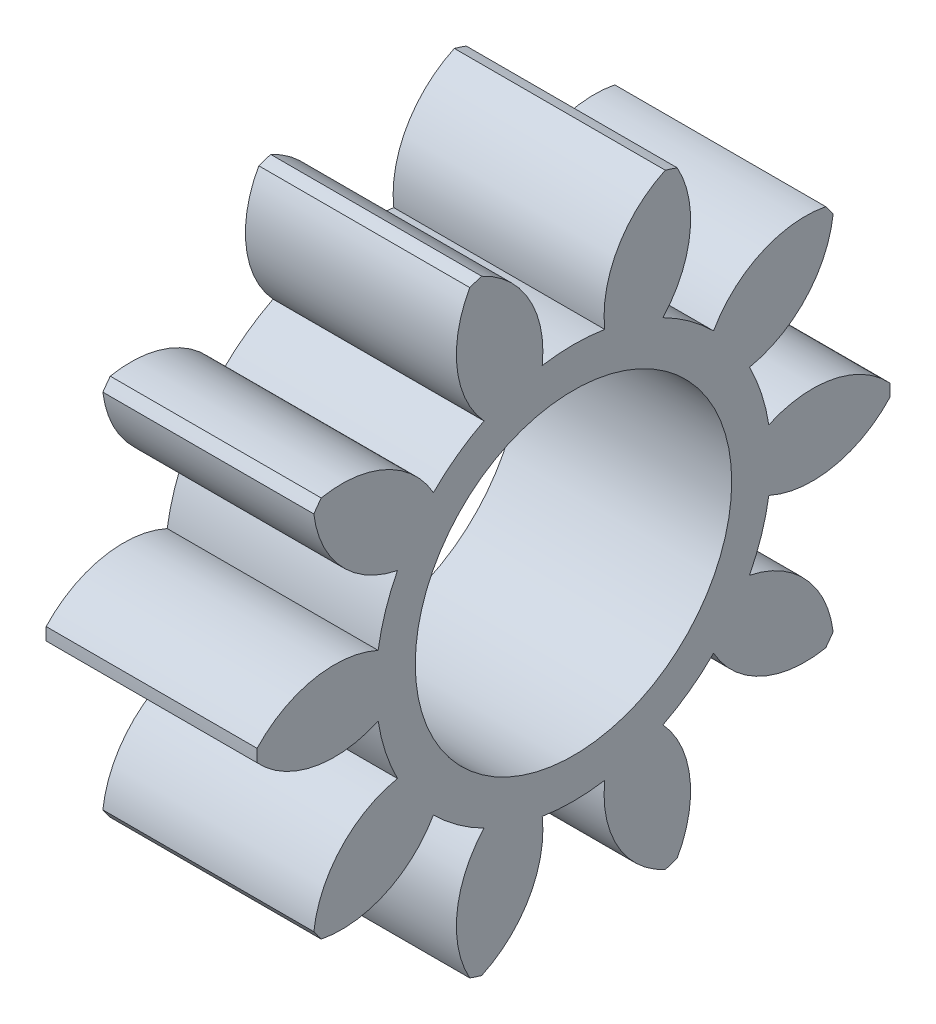
SolidWorks part; units mm, degrees
ref_plane "Plane1" through (0, 0, 0) normal (0, 0, 1) x (1, 0, 0)
ref_plane "Plane2" through (0, 0, 0) normal (0, 1, 0) x (1, 0, 0)
ref_plane "Plane3" through (0, 0, 0) normal (1, 0, 0) x (0, 0, -1)
other "Configuration Table"
sketch "HoldingSke" plane through (0, 0, 0) normal (0, 1, 0) x (1, 0, 0)
  line L0 (0, 0) -> (0.9848, -0.1736)
  line L1 (-15, 0) -> (100, 0) construction
  line L2 (0, 0) -> (-2.1039, 2.3779)
  line L3 (0, 0) -> (-11.863, 4.5341)
  line L4 (0, 0) -> (8.5048, 1.4996)
  line L5 (0, 0) -> (-46.8476, -17.4728)
  line L6 (0, 0) -> (-3.3159, -2.2372)
  line L7 (-2.1039, 2.3779) -> (8.6586, 51.2059)
  line L8 (-76.2, 54.61) -> (-75.2, 54.61)
  line L9 (-71.009, 38.7566) -> (-53.1078, 45.2721)
  line L10 (-76.2, 71.12) -> (104.1128, 71.12)
  line L11 (0, 0) -> (-4, 0)
  line L12 (-76.2, 101.6) -> (-76.162, 101.6)
  line L13 (24.9733, 27.94) -> (52.9518, 28.4284)
  line L14 (24.9733, 27.94) -> (24.9743, 27.94)
  line L15 (24.9733, 27.94) -> (100.4006, 29.5858)
  line L16 (-63.627, -1) -> (-12.827, -1)
  circle A0 centre (0, 0) radius 3
  circle A1 centre (0, 0) radius 3.749
  circle A2 centre (0, 0) radius 37.5
  circle A3 centre (0, 0) radius 3
  dimension "Num_teeth" = 10
  dimension "Pitch_radius" = 180.3128
  dimension "Width" = 4
  dimension "Thickness" = 4
sketch "BasProSke" plane through (0, 0, 0) normal (0, 1, 0) x (1, 0, 0)
  line L0 (-10, 0) -> (60, 0) construction
  line L1 (0, 0) -> (0, 6)
  line L2 (0, 0) -> (4, 0)
  line L3 (4, 0) -> (4, 6)
  line L4 (4, 6) -> (0, 6)
  dimension "Thickness" = 4
  dimension "Diameter" = 12
revolve "Base-Revolve" add sketch "BasProSke" angle 360 about L0
sketch "TooCutSke" plane through (0, 0, 0) normal (1, 0, 0) x (0, 0, -1)
  line L1 (0, 0) -> (0, 107) construction
  line L2 (0, 0) -> (-0.8485, 4.9275) construction
  line L3 (0, 0) -> (-3.0584, 9.4126) construction
  line L4 (-0.8485, 4.9275) -> (-1.5292, 4.7063) construction
  arc A0 (0.5928, 3.7018) -> (-0.5928, 3.7018) centre (0, 0) ccw
  arc A1 (1.7758, 5.7578) -> (-1.7758, 5.7578) centre (0, 0) ccw
  circle A2 centre (0, 0) radius 5 construction
  circle A3 centre (0, 0) radius 4.6985 construction
  arc A4 (-0.5928, 3.7018) -> (-1.7758, 5.7578) centre (-2.5801, 3.9267) ccw
  arc A5 (1.7758, 5.7578) -> (0.5928, 3.7018) centre (2.5801, 3.9267) ccw
extrude "ToothCut" cut sketch "TooCutSke" along normal through all
fillet "Breaks" [suppressed] radius 0.02 tangent propagation no
fillet "RootFillets" [suppressed] radius 0.251
pattern_circular "TeethCuts" count 10 every 36 about axis through (-10, 0, 0) along (1, 0, 0) of "ToothCut", "RootFillets", "Breaks"
sketch "HubNeaOneSke" plane through (0, 0, 0) normal (-1, 0, 0) x (0, 0, 1)
  circle A0 centre (0, 0) radius 3.749
  dimension "Diameter" = 7.498
extrude "HubNearOne" [suppressed] add sketch "HubNeaOneSke" along normal blind 46.0001
sketch "HubNeaBotSke" plane through (0, 0, 0) normal (-1, 0, 0) x (0, 0, 1)
  circle A0 centre (0, 0) radius 3.749
  dimension "Diameter" = 7.498
extrude "HubNearBoth" [suppressed] add sketch "HubNeaBotSke" along normal blind 23
ref_plane "FarPln" through (4, 0, 0) normal (1, 0, 0) x (0, 0, -1)
sketch "HubFarSke" plane through (4, 0, 0) normal (1, 0, 0) x (0, 0, -1)
  circle A0 centre (0, 0) radius 3.749
  dimension "Diameter" = 7.498
extrude "HubFar" [suppressed] add sketch "HubFarSke" along normal blind 23
sketch "BorSke" plane through (0, 0, 0) normal (1, 0, 0) x (0, 0, -1)
  circle A0 centre (0, 0) radius 3
  dimension "Diameter" = 6
extrude "Bore" cut sketch "BorSke" along normal mid plane 100.0001
sketch "KeySke" plane through (0, 0, 0) normal (1, 0, 0) x (0, 0, -1)
  line L0 (-1, 0) -> (-1, 4)
  line L1 (-1, 4) -> (1, 4)
  line L2 (1, 4) -> (1, 0)
  line L3 (0, 0) -> (0, 34) construction
  line L4 (-1, 0) -> (1, 0)
  dimension "Width" = 2
extrude "Keyway" [suppressed] cut sketch "KeySke" along normal mid plane 100.0001
pattern_circular "Keyway2" [suppressed] count 2 every 90 about axis through (-10, 0, 0) along (1, 0, 0)
ref_axis "Axis1" through (4, 0, 0) along (-1, 0, 0)
sketch "Sketch1" plane through (0, 0, 0) normal (-1, 0, 0) x (0, 0, 1)
  line L0 (1, 2.8284) -> (1, -2.8284)
  line L1 (1, 0) -> (-3, 0) construction
  circle A0 centre (0, 0) radius 3 construction
  arc A1 (1, 2.8284) -> (1, -2.8284) centre (0, 0) cw
  dimension "D1" = 4
equation "' \"Module@HoldingSke\" = 6.35"
equation "' \"Num_teeth@HoldingSke\" = 12"
equation "' \"Ap@HoldingSke\" =  20"
equation "' \"Ap@HoldingSke\" = 20"
equation "' \"Width@HoldingSke\" = 0.5 * 25.4"
equation "' \"Hub_dia@HoldingSke\"= 1 * 25.4"
equation "' \"Hub_dia@HoldingSke\" = 1 * 25.4"
equation "' \"Overall_len@HoldingSke\" = 1.0 * 25.4"
equation "' \"Bore@HoldingSke\" = 0.75 * 25.4"
equation "' \"T_dim@HoldingSke\" = 0.1 * 25.4"
equation "' \"Width@KeySke\" = 0.25 * 25.4"
equation "' \"Show_teeth@HoldingSke\" = 13"
equation "' \"Backlash@HoldingSke\" = 0.009 * 25.4"
equation "' \"Addendum_fac@HoldingSke\" = 1.0"
equation "' \"Dedendum_fac@HoldingSke\" = 1.25"
equation "' \"Dedendum_add@HoldingSke\" = 0.00005 * 25.4"
equation "' \"Clearance_fac@HoldingSke\" = 0.25"
equation "\"Pitch@HoldingSke\" = 1 / \"Module@HoldingSke\""
equation "\"Overcut_dia@TooCutSke\" = (\"Num_teeth@HoldingSke\" + 2 * \"Addendum_fac@HoldingSke\") / \"Pitch@HoldingSke\" + 0.002 * 25.4"
equation "\"Pitch_dia@TooCutSke\" = \"Num_teeth@HoldingSke\" / \"Pitch@HoldingSke\""
equation "\"Base_dia@TooCutSke\" = \"Num_teeth@HoldingSke\" / \"Pitch@HoldingSke\" * cos((\"Ap@HoldingSke\"  * 3.14159265 / 180))"
equation "\"Root_dia@TooCutSke\" = (\"Num_teeth@HoldingSke\" + 2) / \"Pitch@HoldingSke\" - 2 * (\"Addendum_fac@HoldingSke\" + \"Dedendum_fac@HoldingSke\") / \"Pitch@HoldingSke\" - \"Dedendum_add@HoldingSke\" * 2"
equation "\"Half_ang@TooCutSke\" = 180 / \"Num_teeth@HoldingSke\""
equation "\"Half_CT@TooCutSke\" = \"Num_teeth@HoldingSke\" / \"Pitch@HoldingSke\" * sin((3.14159265 / 2 / \"Num_teeth@HoldingSke\")) / 2 - 7 * \"Backlash@HoldingSke\" / 4"
equation "\"Flank_rad@TooCutSke\" = \"Num_teeth@HoldingSke\" / \"Pitch@HoldingSke\" / 5"
equation "\"Radius@RootFillets\" = \"Clearance_fac@HoldingSke\" / \"Pitch@HoldingSke\" + \"Dedendum_add@HoldingSke\""
equation "\"Break_rad@Breaks\" = 0.02 / \"Pitch@HoldingSke\""
equation "\"Thickness@HoldingSke\" = \"Width@HoldingSke\""
equation "\"OAL@HoldingSke\" = \"Thickness@HoldingSke\""
equation "\"MHD@HoldingSke\" = (\"Num_teeth@HoldingSke\" + 2) / \"Pitch@HoldingSke\" - 2 * (\"Addendum_fac@HoldingSke\" + \"Dedendum_fac@HoldingSke\")  / \"Pitch@HoldingSke\" - \"Dedendum_add@HoldingSke\" * 2"
equation "\"MBD@HoldingSke\" = (\"Num_teeth@HoldingSke\" + 2) / \"Pitch@HoldingSke\" - 2 * (\"Addendum_fac@HoldingSke\" + \"Dedendum_fac@HoldingSke\")  / \"Pitch@HoldingSke\" - \"Dedendum_add@HoldingSke\" * 2 - 0.002 * 25.4"
equation "\"MHD@HoldingSke\" = ((sgn( \"MHD@HoldingSke\" - \"Hub_dia@HoldingSke\" )-1)*( \"MHD@HoldingSke\" - \"Hub_dia@HoldingSke\" ))/-2+ \"Hub_dia@HoldingSke\""
equation "\"MBD@HoldingSke\" = ((sgn( \"MBD@HoldingSke\" - \"Bore@HoldingSke\" )-1)*( \"MBD@HoldingSke\" - \"Bore@HoldingSke\" ))/-2+ \"Bore@HoldingSke\""
equation "\"OAL@HoldingSke\" = ((sgn( \"OAL@HoldingSke\" - \"Overall_len@HoldingSke\" )+1)*( \"OAL@HoldingSke\" - \"Overall_len@HoldingSke\" ))/2 + \"Overall_len@HoldingSke\" + 0.000002 * 25.4"
equation "\"Num_teeth@TeethCuts\" = int( \"Show_teeth@HoldingSke\" ) + 1"
equation "\"Num_teeth@TeethCuts\" = ((sgn( \"Num_teeth@TeethCuts\" - \"Num_teeth@HoldingSke\" )-1)*( \"Num_teeth@TeethCuts\" - \"Num_teeth@HoldingSke\" ))/-2+ \"Num_teeth@HoldingSke\""
equation "\"Num_teeth@TeethCuts\" = ((sgn( \"Num_teeth@TeethCuts\" - 2.0)+1)*( \"Num_teeth@TeethCuts\" - 2.0))/2 +2.0"
equation "\"Angle@TeethCuts\" = 360.0 / \"Num_teeth@HoldingSke\""
equation "\"Diameter@BasProSke\" = (\"Num_teeth@HoldingSke\" + 2 * \"Addendum_fac@HoldingSke\") / \"Pitch@HoldingSke\""
equation "\"Thickness@BasProSke\"  = \"Thickness@HoldingSke\""
equation "' \"Fillet_rad@BasProSke\" =  \"Thickness@HoldingSke\" * 0.05"
equation "' \"Fillet_rad@BasProSke\" = \"Thickness@HoldingSke\" * 0.05"
equation "\"MHD@HoldingSke\" = ((sgn( \"MHD@HoldingSke\" - \"Root_dia@TooCutSke\" )-1)*( \"MHD@HoldingSke\" - \"Root_dia@TooCutSke\" ))/-2+ \"Root_dia@TooCutSke\""
equation "\"Diameter@HubNeaOneSke\" = \"MHD@HoldingSke\""
equation "\"Length@HubNearOne\" = \"OAL@HoldingSke\" - \"Thickness@BasProSke\""
equation "\"Diameter@HubNeaBotSke\" = \"MHD@HoldingSke\""
equation "\"Length@HubNearBoth\" = ( \"OAL@HoldingSke\" - \"Thickness@BasProSke\" ) / 2.0"
equation "\"Thickness@FarPln\" = \"Thickness@BasProSke\""
equation "\"Diameter@HubFarSke\" = \"MHD@HoldingSke\""
equation "\"Length@HubFar\" = ( \"OAL@HoldingSke\" - \"Thickness@BasProSke\" ) / 2.0"
equation "\"Diameter@BorSke\" = \"MBD@HoldingSke\""
equation "\"D1@Bore\" = \"OAL@HoldingSke\" * 2.0"
equation "\"D1@Keyway\" = \"OAL@HoldingSke\" * 2.0"
equation "\"Offset@KeySke\" = \"T_dim@HoldingSke\" + \"MBD@HoldingSke\" / 2.0"
